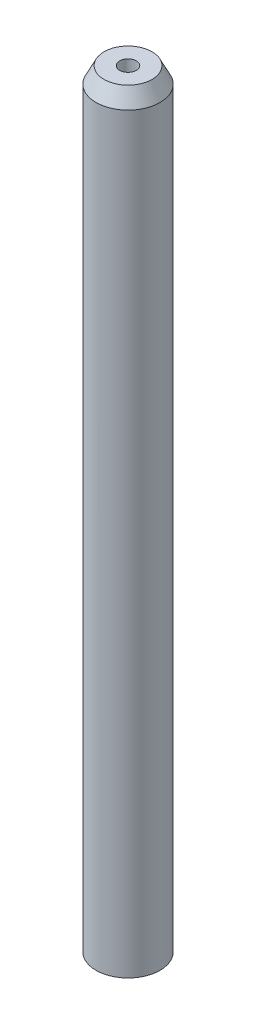
SolidWorks part; units mm, degrees
ref_plane "Front Plane" through (0, 0, 0) normal (0, 0, 1) x (1, 0, 0)
ref_plane "Top Plane" through (0, 0, 0) normal (0, 1, 0) x (1, 0, 0)
ref_plane "Right Plane" through (0, 0, 0) normal (1, 0, 0) x (0, 0, -1)
sketch "Sketch1" plane through (0, 0, 0) normal (0, 1, 0) x (1, 0, 0)
  circle A0 centre (0, 0) radius 6.35
  dimension "D1" = 12.7
extrude "PostBody" add sketch "Sketch1" along normal blind 152.4
sketch "Sketch4" plane through (0, 0, 0) normal (0, 0, 1) x (1, 0, 0)
  line L5 (6.35, 152.4) -> (6.35, 149.225)
  line L6 (6.35, 152.4) -> (-6.35, 152.4) construction
  line L7 (6.35, 0) -> (6.35, 152.4) construction
  line L8 (6.35, 149.225) -> (4.7625, 152.4)
  line L9 (4.7625, 152.4) -> (6.35, 152.4)
  point P7 (6.35, 152.4)
  dimension "D1" = 1.5875
  dimension "D2" = 3.175
sketch "Sketch5" plane through (0, 152.4, 0) normal (0, 1, 0) x (1, 0, 0)
  circle A0 centre (0, 0) radius 4.7487
sweep "TopCut" cut profiles "Sketch4" path "Sketch5"
hole_wizard "M4x0.7 Tapped Hole1" positions "Sketch6" profile "Sketch7" tap size "M4x0.7" standard "ANSI Metric"
sketch "Sketch6" plane through (0, 152.4, 0) normal (0, 1, 0) x (1, 0, 0)
  point P0 (0, 0)
sketch "Sketch7" plane through (0, 152.4, 0) normal (1, 0, 0) x (0, 0, 1)
  line L0 (0, 0) -> (0, 10.5164)
  line L1 (0, 10.5164) -> (1.65, 9.525)
  line L2 (1.65, 9.525) -> (1.65, 0)
  line L5 (1.65, 0) -> (0, 0)
  line L10 (0, 10.5164) -> (-1.65, 9.525) construction
  line L11 (0, -6.35) -> (0, 107.95) construction
  dimension "Tap Drill Dia." = 3.3
  dimension "Tap Drill Depth" = 9.525
  dimension "Drill Angle" = 118
cosmetic thread "Hole Thread2" parameters "D1"=7.874, "D2"=4
hole_wizard "M6x1.0 Tapped Hole1" positions "Sketch8" profile "Sketch9" tap size "M6x1.0" standard "ANSI Metric"
sketch "Sketch8" plane through (0, 0, 0) normal (0, -1, 0) x (-1, 0, 0)
  point P0 (0, 0)
sketch "Sketch9" plane through (0, 0, 0) normal (1, 0, 0) x (0, 0, -1)
  line L0 (0, 0) -> (0, 14.2022)
  line L1 (0, 14.2022) -> (2.5, 12.7)
  line L2 (2.5, 12.7) -> (2.5, 0)
  line L5 (2.5, 0) -> (0, 0)
  line L10 (0, 14.2022) -> (-2.5, 12.7) construction
  line L11 (0, -6.35) -> (0, 107.95) construction
  dimension "Tap Drill Dia." = 5
  dimension "Tap Drill Depth" = 12.7
  dimension "Drill Angle" = 118
cosmetic thread "Hole Thread1" parameters "D1"=11.938, "D2"=6
equation "\"post_diameter\"=0.5"
equation "\"D1@Sketch1\"=\"post_diameter\""
equation "\"post_height\"=6"
equation "\"D1@PostBody\" = \"post_height\""
